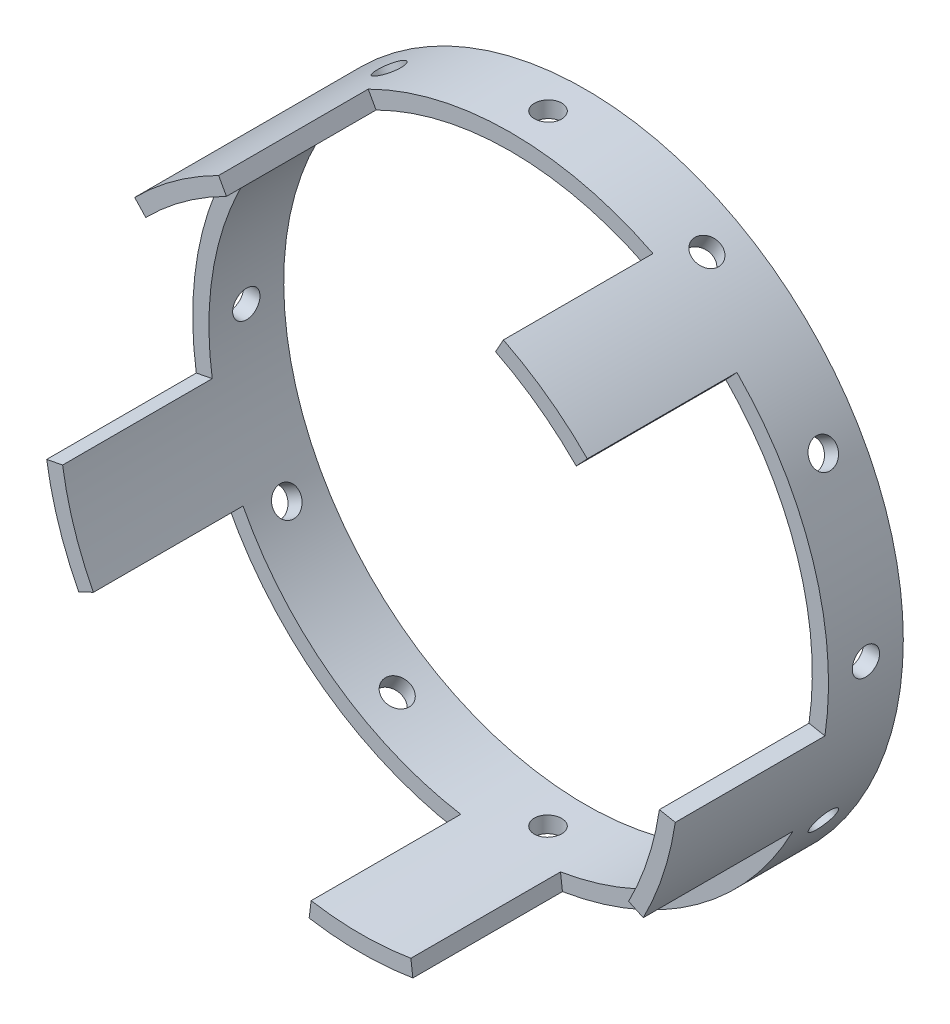
SolidWorks part; units mm, degrees
ref_plane "Front Plane" through (0, 0, 0) normal (0, 0, 1) x (1, 0, 0)
ref_plane "Top Plane" through (0, 0, 0) normal (0, 1, 0) x (1, 0, 0)
ref_plane "Right Plane" through (0, 0, 0) normal (1, 0, 0) x (0, 0, -1)
sketch "Sketch1" plane through (0, 0, 0) normal (0, 0, 1) x (1, 0, 0)
  circle A0 centre (0, 0) radius 76.835
  circle A1 centre (0, 0) radius 80.9625
  dimension "D1" = 153.67
  dimension "D2" = 161.925
extrude "Boss-Extrude1" add sketch "Sketch1" along normal blind 19.05
sketch "Sketch3" plane through (0, 0, 19.05) normal (0, 0, 1) x (1, 0, 0)
  line L0 (-13.208, -79.8779) -> (-12.7, -75.7781)
  line L1 (12.7, -75.7781) -> (13.208, -79.8779)
  line L2 (-68.1448, -35.4952) -> (-71.8869, -37.2452)
  line L3 (-80.0499, -12.1221) -> (-75.9938, -11.3383)
  line L4 (-54.8158, 53.8409) -> (-57.6365, 56.8591)
  line L5 (-36.2655, 72.386) -> (-34.2668, 68.7707)
  line L6 (34.2668, 68.7707) -> (36.2655, 72.386)
  line L7 (57.6365, 56.8591) -> (54.8158, 53.8409)
  line L8 (75.9938, -11.3383) -> (80.0499, -12.1221)
  line L9 (71.8869, -37.2452) -> (68.1448, -35.4952)
  arc A0 (-12.7, -75.7781) -> (12.7, -75.7781) centre (0, 0) ccw
  circle A1 centre (0, 0) radius 76.835 construction
  arc A2 (13.208, -79.8779) -> (-13.208, -79.8779) centre (0, 0) cw
  circle A3 centre (0, 0) radius 80.9625 construction
  arc A4 (-71.8869, -37.2452) -> (-80.0499, -12.1221) centre (0, 0) cw
  arc A5 (-75.9938, -11.3383) -> (-68.1448, -35.4952) centre (0, 0) ccw
  arc A6 (-57.6365, 56.8591) -> (-36.2655, 72.386) centre (0, 0) cw
  arc A7 (-34.2668, 68.7707) -> (-54.8158, 53.8409) centre (0, 0) ccw
  arc A8 (36.2655, 72.386) -> (57.6365, 56.8591) centre (0, 0) cw
  arc A9 (54.8158, 53.8409) -> (34.2668, 68.7707) centre (0, 0) ccw
  arc A10 (80.0499, -12.1221) -> (71.8869, -37.2452) centre (0, 0) cw
  arc A11 (68.1448, -35.4952) -> (75.9938, -11.3383) centre (0, 0) ccw
  point P28 (0, 0)
  dimension "D1" = 12.7
  dimension "D2" = 12.7
  dimension "D3" = 13.208
  dimension "D4" = 13.208
  dimension "D5" = 5
extrude "Boss-Extrude2" add sketch "Sketch3" along normal blind 38.1
sketch "Sketch2" plane through (0, 0, 0) normal (0, 1, 0) x (1, 0, 0)
  line L0 (76.835, 0) -> (-76.835, 0) construction
  line L1 (0, -2.0807) -> (0, -15.8358) construction
  circle A0 centre (0, -9.525) radius 3.4782
  dimension "D1" = 9.525
extrude "Cut-Extrude1" cut sketch "Sketch2" against normal through all
ref_axis "Axis1" through (0, 0, 2.0807) along (0, 0, 1)
pattern_circular "CirPattern1" count 12 over 360 about axis through (0, 0, 2.0807) along (0, 0, 1) of "Cut-Extrude1"
